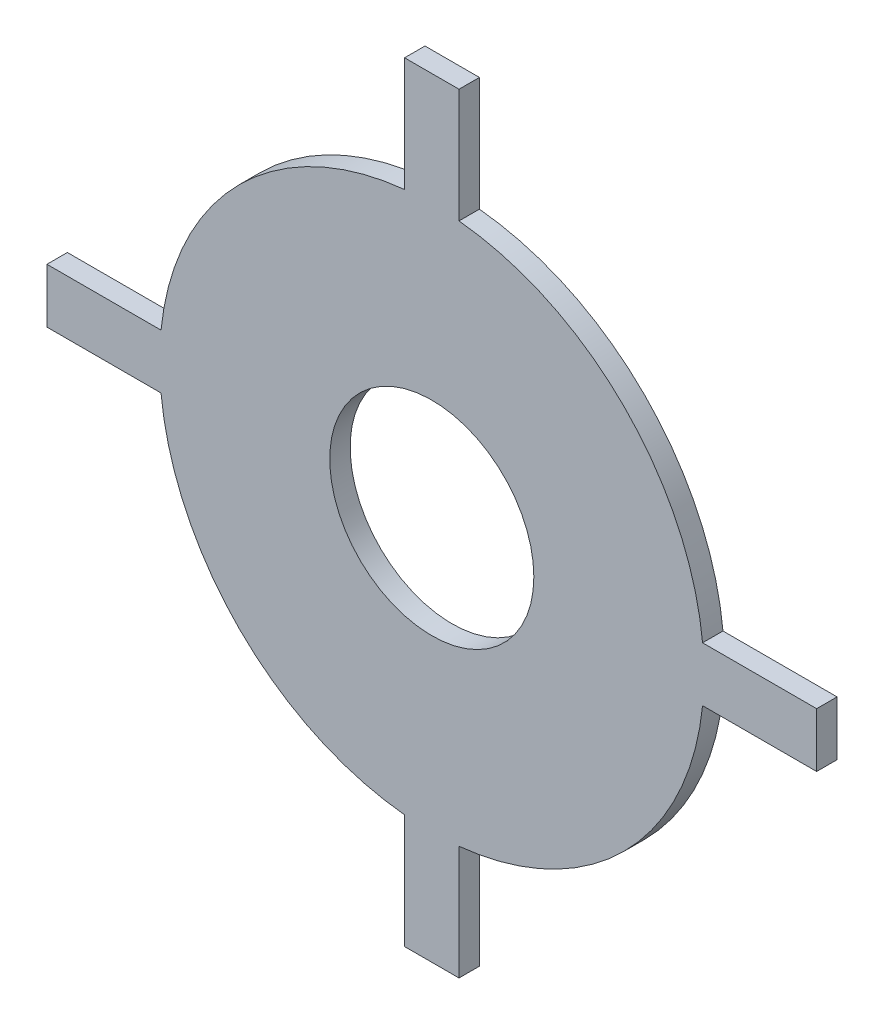
SolidWorks part; units mm, degrees
ref_plane "前视基准面" through (0, 0, 0) normal (0, 0, 1) x (1, 0, 0)
ref_plane "上视基准面" through (0, 0, 0) normal (0, 1, 0) x (1, 0, 0)
ref_plane "右视基准面" through (0, 0, 0) normal (1, 0, 0) x (0, 0, -1)
other "Configuration Table"
sketch "草图1" plane through (0, 0, 0) normal (0, 0, 1) x (1, 0, 0)
  circle A0 centre (0, 0) radius 20
  circle A1 centre (0, 0) radius 7.5
  dimension "D1" = 40
  dimension "D2" = 15
extrude "凸台-拉伸1" add sketch "草图1" along normal blind 1.5
sketch "草图2" plane through (0, 0, 0) normal (0, 0, 1) x (1, 0, 0)
  line L1 (19, -2) -> (28.2843, -2)
  line L2 (19, -2) -> (19, 2)
  line L3 (19, 2) -> (28.2843, 2)
  line L4 (28.2843, -2) -> (28.2843, 2)
  line L6 (2, 19) -> (-2, 19)
  line L7 (2, 19) -> (2, 28.2843)
  line L8 (2, 28.2843) -> (-2, 28.2843)
  line L9 (-2, 19) -> (-2, 28.2843)
  line L11 (-19, 2) -> (-28.2843, 2)
  line L12 (-19, 2) -> (-19, -2)
  line L13 (-19, -2) -> (-28.2843, -2)
  line L14 (-28.2843, 2) -> (-28.2843, -2)
  line L16 (-2, -19) -> (2, -19)
  line L17 (-2, -19) -> (-2, -28.2843)
  line L18 (-2, -28.2843) -> (2, -28.2843)
  line L19 (2, -19) -> (2, -28.2843)
  dimension "D1" = 56.5685
  dimension "D2" = 4
extrude "凸台-拉伸2" add sketch "草图2" along normal blind 1.5
